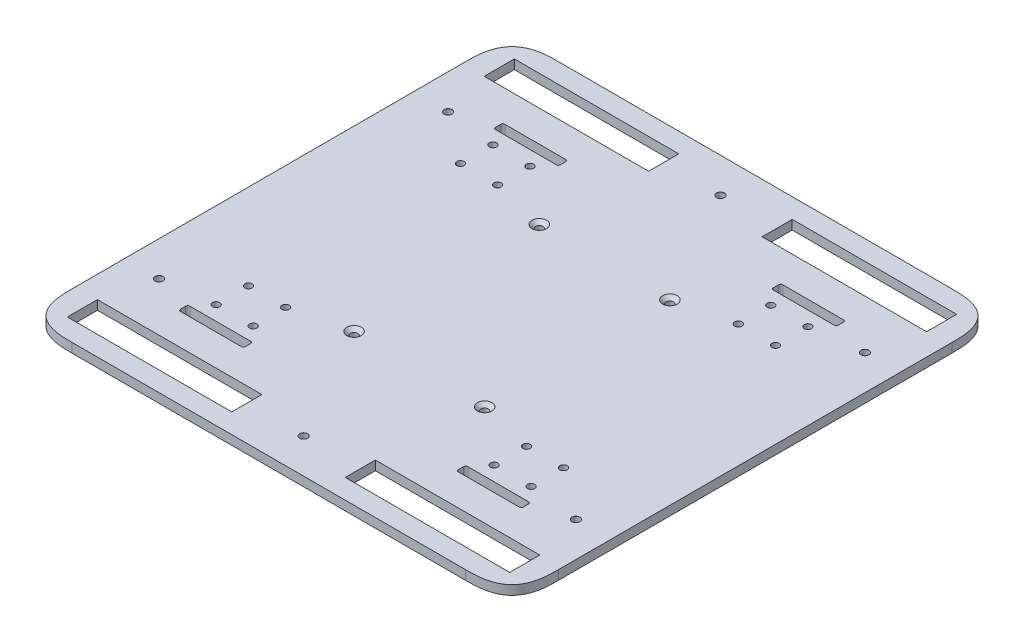
SolidWorks part; units mm, degrees
ref_plane "Спереди" through (0, 0, 0) normal (0, 0, 1) x (1, 0, 0)
ref_plane "Сверху" through (0, 0, 0) normal (0, 1, 0) x (1, 0, 0)
ref_plane "Справа" through (0, 0, 0) normal (1, 0, 0) x (0, 0, -1)
sketch "Эскиз1" plane through (0, 0, 0) normal (0, 1, 0) x (1, 0, 0)
  line L1 (-150, -150) -> (150, -150) construction
  line L2 (-150, -150) -> (-150, 150) construction
  line L3 (-150, 150) -> (150, 150) construction
  line L4 (150, -150) -> (150, 150) construction
  line L5 (-150, -150) -> (150, 150) construction
  line L6 (-150, 150) -> (150, -150) construction
  line L7 (-105, -105) -> (105, -105)
  line L8 (-105, -105) -> (-105, 105)
  line L9 (-105, 105) -> (105, 105)
  line L10 (105, -105) -> (105, 105)
  line L11 (-105, -105) -> (105, 105) construction
  line L12 (-105, 105) -> (105, -105) construction
  circle A0 centre (0, 0) radius 150 construction
  point P0 (0, 0)
  point P6 (0, 0)
  dimension "D1" = 300
  dimension "D2" = 210
extrude "Бобышка-Вытянуть1" add sketch "Эскиз1" along normal blind 4 contours L8 L9 L10 L7
fillet "Скругление1" radius 20 4 edges at (-105, 2, -105) (105, 2, -105) (105, 2, 105) (-105, 2, 105) curvature continuous yes
sketch "Эскиз17" plane through (0, 4, 0) normal (0, 1, 0) x (1, 0, 0)
  line L0 (-47, 69) -> (-73, 69) construction
  line L1 (-47, 67) -> (-73, 67) construction
  line L2 (-47, 69) -> (-73, 69) construction
  line L3 (-47, 67) -> (-73, 67) construction
  line L4 (0, -52.0318) -> (0, 52.0318) construction
  line L5 (-73, 67) -> (-47, 67) construction
  line L6 (-73, 67) -> (-73, 69) construction
  line L7 (-73, 69) -> (-47, 69) construction
  line L8 (-47, 67) -> (-47, 69) construction
  line L9 (-73, 67) -> (-47, 69) construction
  line L10 (-73, 69) -> (-47, 67) construction
  line L11 (-74, 70) -> (-46, 70)
  line L12 (-46, 66) -> (-46, 70)
  line L13 (-74, 66) -> (-46, 66)
  line L14 (-74, 66) -> (-74, 70)
  line L15 (46, 66) -> (46, 70)
  line L16 (74, 66) -> (46, 66)
  line L17 (74, 66) -> (74, 70)
  line L18 (74, 70) -> (46, 70)
  line L20 (-52.0318, 0) -> (52.0318, 0) construction
  line L21 (46, -66) -> (46, -70)
  line L22 (74, -66) -> (46, -66)
  line L23 (74, -66) -> (74, -70)
  line L24 (74, -70) -> (46, -70)
  line L25 (-46, -66) -> (-46, -70)
  line L26 (-74, -66) -> (-46, -66)
  line L27 (-74, -66) -> (-74, -70)
  line L28 (-74, -70) -> (-46, -70)
  point P4 (-60, 68)
  dimension "D1" = 1
extrude "Вырез-Вытянуть2" cut sketch "Эскиз17" against normal up to next
fillet "Скругление3" radius 1 16 edges at (74, 2, -66) (46, 2, -66) (46, 2, -70) (74, 2, -70) (-46, 2, -70) (-74, 2, -70) (-74, 2, -66) (-46, 2, -66) (74, 2, 70) (74, 2, 66) (46, 2, 66) (46, 2, 70) (-74, 2, 70) (-74, 2, 66) (-46, 2, 70) (-46, 2, 66) curvature continuous yes
hole_wizard "Сверло под метчик  спиральное M31" positions "Эскиз33" profile "Эскиз34" hole size "M3x0.5" standard "DIN"
sketch "Эскиз33" plane through (0, 4, 0) normal (0, 1, 0) x (1, 0, 0)
  point P0 (-68, 59.75)
  point P3 (-52, 59.75)
  point P6 (-68, 45.75)
  point P9 (-52, 45.75)
  point P12 (-52, -59.75)
  point P15 (-52, -45.75)
  point P20 (-68, -59.75)
  point P23 (52, -59.75)
  point P26 (52, -45.75)
  point P29 (68, -59.75)
  point P32 (68, -45.75)
  point P35 (52, 59.75)
  point P42 (52, 45.75)
  point P45 (-68, -45.75)
  point P48 (68, 45.75)
  point P51 (68, 59.75)
sketch "Эскиз34" plane through (-68, 4, -59.75) normal (1, 0, 0) x (0, 0, 1)
  line L0 (0, 0) -> (0, 8.9464)
  line L1 (0, 8.9464) -> (1.575, 8)
  line L2 (1.575, 8) -> (1.575, 0)
  line L5 (1.575, 0) -> (0, 0)
  line L10 (0, 8.9464) -> (-1.575, 8) construction
  line L11 (0, -6.35) -> (0, 107.95) construction
  dimension "Диаметр отверстия" = 3.15
  dimension "Глубина отверстия" = 8
  dimension "Угол заточки сверла" = 118
hole_wizard "Отверстие с зазором M35" positions "Эскиз39" profile "Эскиз40" hole size "M3" standard "DIN" end condition through all
sketch "Эскиз39" plane through (0, 4, 0) normal (0, 1, 0) x (1, 0, 0)
  point P0 (90, 62.4)
  point P3 (-90, 62.4)
  point P6 (-90, -62.4)
  point P9 (90, -62.4)
  point P12 (0, -90)
  point P15 (0, 90)
sketch "Эскиз40" plane through (90, 4, -62.4) normal (1, 0, 0) x (0, 0, 1)
  line L0 (0, 0) -> (0, 4.05)
  line L1 (0, 4.05) -> (1.7, 4.05)
  line L2 (1.7, 4.05) -> (1.7, 0.025)
  line L3 (1.7, 0.025) -> (1.725, 0)
  line L5 (1.725, 0) -> (0, 0)
  line L6 (-1.7, 0.025) -> (-1.725, 0) construction
  line L11 (0, -6.35) -> (0, 107.95) construction
  dimension "Диаметр сквозного отверстия" = 3.4
  dimension "Глубина сквозного отверстия" = 4.05
  dimension "Диаметр передней зенковки" = 3.45
  dimension "Угол передней зенковки" = 90
hole_wizard "Зенковка для винта с полупотайной головкой M31" positions "Эскиз43" profile "Эскиз44" countersink size "M3" standard "DIN"
sketch "Эскиз43" plane through (0, 4, 0) normal (0, 1, 0) x (1, 0, 0)
  arc A0 (28.2, 41.55) -> (28.2, 38.45) centre (28.2, 40) ccw construction
  arc A1 (28.2, 38.45) -> (28.2, 41.55) centre (28.2, 40) ccw construction
  arc A2 (-28.2, 38.45) -> (-28.2, 41.55) centre (-28.2, 40) ccw construction
  arc A3 (-28.2, 41.55) -> (-28.2, 38.45) centre (-28.2, 40) ccw construction
  arc A4 (28.2, 41.55) -> (28.2, 38.45) centre (28.2, 40) ccw construction
  arc A5 (28.2, 38.45) -> (28.2, 41.55) centre (28.2, 40) ccw construction
  arc A6 (-28.2, 38.45) -> (-28.2, 41.55) centre (-28.2, 40) ccw construction
  arc A7 (-28.2, 41.55) -> (-28.2, 38.45) centre (-28.2, 40) ccw construction
  arc A8 (-28.2, -41.55) -> (-28.2, -38.45) centre (-28.2, -40) ccw construction
  arc A9 (-28.2, -38.45) -> (-28.2, -41.55) centre (-28.2, -40) ccw construction
  arc A10 (28.2, -41.55) -> (28.2, -38.45) centre (28.2, -40) ccw construction
  arc A11 (28.2, -38.45) -> (28.2, -41.55) centre (28.2, -40) ccw construction
  arc A12 (-28.2, -41.55) -> (-28.2, -38.45) centre (-28.2, -40) ccw construction
  arc A13 (-28.2, -38.45) -> (-28.2, -41.55) centre (-28.2, -40) ccw construction
  arc A14 (28.2, -41.55) -> (28.2, -38.45) centre (28.2, -40) ccw construction
  arc A15 (28.2, -38.45) -> (28.2, -41.55) centre (28.2, -40) ccw construction
  point P1 (28.2, 40)
  point P7 (-28.2, 40)
  point P19 (-28.2, -40)
  point P25 (28.2, -40)
sketch "Эскиз44" plane through (28.2, 4, -40) normal (1, 0, 0) x (0, 0, 1)
  line L0 (0, 0) -> (0, 4.9614)
  line L1 (0, 4.9614) -> (1.6, 4)
  line L2 (1.6, 4) -> (1.6, 1.55)
  line L3 (1.6, 1.55) -> (3.15, 0)
  line L5 (3.15, 0) -> (0, 0)
  line L6 (-1.6, 1.55) -> (-3.15, 0) construction
  line L10 (0, 4.9614) -> (-1.6, 4) construction
  line L11 (0, -6.35) -> (0, 107.95) construction
  dimension "Диаметр отверстия" = 3.2
  dimension "Глубина отверстия" = 4
  dimension "Диаметр передней зенковки" = 6.3
  dimension "Угол передней зенковки" = 90
  dimension "Угол заточки сверла" = 118
sketch "Эскиз45" plane through (0, 4, 0) normal (0, 1, 0) x (1, 0, 0)
  line L0 (-52.0318, 0) -> (52.0318, 0) construction
  line L1 (-95.5, 96.5) -> (-24.5, 96.5)
  line L2 (-95.5, 96.5) -> (-95.5, 83.5)
  line L3 (-95.5, 83.5) -> (-24.5, 83.5)
  line L6 (-92.5, 85) -> (-27.5, 85) construction
  line L7 (-27.5, 95) -> (-92.5, 95) construction
  line L8 (-24.5, 96.5) -> (-24.5, 83.5)
  line L9 (-95.5, -96.5) -> (-95.5, -83.5)
  line L10 (-95.5, -96.5) -> (-24.5, -96.5)
  line L11 (-24.5, -96.5) -> (-24.5, -83.5)
  line L14 (-92.5, 85) -> (-27.5, 85) construction
  line L15 (-27.5, 95) -> (-92.5, 95) construction
  line L16 (-95.5, -83.5) -> (-24.5, -83.5)
  line L17 (0, -52.0318) -> (0, 52.0318) construction
  line L18 (24.5, -96.5) -> (24.5, -83.5)
  line L19 (95.5, -96.5) -> (95.5, -83.5)
  line L20 (95.5, -83.5) -> (24.5, -83.5)
  line L21 (95.5, -96.5) -> (24.5, -96.5)
  line L22 (95.5, 96.5) -> (95.5, 83.5)
  line L23 (24.5, 96.5) -> (24.5, 83.5)
  line L24 (95.5, 96.5) -> (24.5, 96.5)
  line L25 (95.5, 83.5) -> (24.5, 83.5)
  dimension "D1" = 1.5
  dimension "D2" = 1.5
  dimension "D3" = 3
  dimension "D4" = 3
extrude "Вырез-Вытянуть3" cut sketch "Эскиз45" against normal through all
